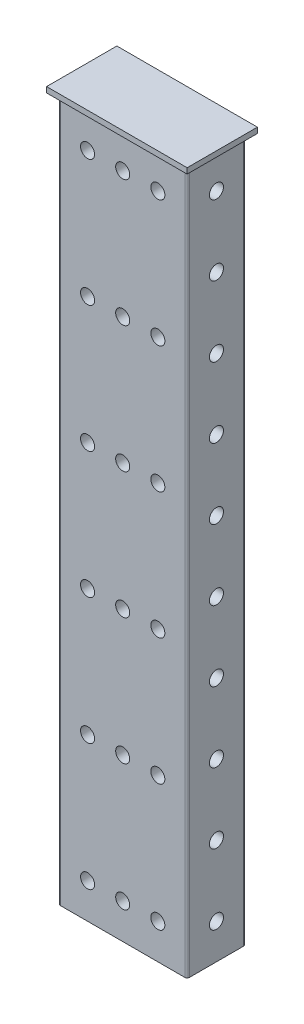
SolidWorks part; units mm, degrees
material "Nylon 101"
ref_plane "Front Plane" through (0, 0, 0) normal (0, 0, 1) x (1, 0, 0)
ref_plane "Top Plane" through (0, 0, 0) normal (0, 1, 0) x (1, 0, 0)
ref_plane "Right Plane" through (0, 0, 0) normal (1, 0, 0) x (0, 0, -1)
sketch "Sketch2" plane through (0, 0, 0) normal (0, 1, 0) x (1, 0, 0)
  line L1 (0, 0) -> (50.8, 0)
  line L2 (0, 0) -> (0, 25.4)
  line L3 (0, 25.4) -> (50.8, 25.4)
  line L12 (50.8, 0) -> (50.8, 25.4)
  line L14 (2.1082, 23.2918) -> (48.6918, 23.2918)
  line L15 (48.6918, 2.1082) -> (48.6918, 23.2918)
  line L16 (2.1082, 2.1082) -> (48.6918, 2.1082)
  line L17 (2.1082, 2.1082) -> (2.1082, 23.2918)
  dimension "D1" = 50.8
  dimension "D3" = 25.4
  dimension "D2" = 2.1082
extrude "Boss-Extrude2" add sketch "Sketch2" along normal blind 2 separate body contours L17 L16 L15 L14 | L16 L17 L14 L15 region at (0.568, 0, -12.7) region at (25.4, 0, -12.7)
extrude "Boss-Extrude3" add sketch "Sketch2<4>" against normal blind 254 contours L17 L16 L15 L14 region at (25.4, 0, -12.7)
sketch "Sketch2<4>" plane through (0, 0, 0) normal (0, 1, 0) x (1, 0, 0) same geometry as "Sketch2"
fillet "Fillet3" radius 0.8106 4 edges at (2.1082, -127, -23.2918) (48.6918, -127, -2.1082) (2.1082, -127, -2.1082) (48.6918, -127, -23.2918)
sketch "Sketch3" plane through (48.6918, 0, 0) normal (1, 0, 0) x (0, 0, -1)
  line L0 (2.9188, 0) -> (22.4812, 0) construction
  line L1 (2.9188, -254) -> (22.4812, -254) construction
  line L3 (12.7, 0) -> (12.7, -254) construction
  circle A0 centre (12.7, -12.7) radius 2.54
  point P4 (11.5292, -248.866)
  point P7 (12.7635, -2.6535)
  dimension "D3" = 5.08
  dimension "D1" = 12.7
extrude "Cut-Extrude1" cut sketch "Sketch3" against normal through all
sketch "Sketch4" plane through (0, 0, -23.2918) normal (0, 0, -1) x (-1, 0, 0)
  line L0 (-47.8812, -12.7) -> (-2.9188, -12.7) construction
  line L1 (-47.8812, 0) -> (-47.8812, -254) construction
  line L2 (-2.9188, -254) -> (-2.9188, 0) construction
  line L3 (-2.9188, 0) -> (-47.8812, 0) construction
  circle A0 centre (-25.4, -12.7) radius 2.54
  circle A1 centre (-38.1, -12.7) radius 2.54
  circle A2 centre (-12.7, -12.7) radius 2.54
  dimension "D2" = 5.08
  dimension "D1" = 12.7
  dimension "D3" = 12.7
  dimension "D4" = 12.7
extrude "Cut-Extrude2" cut sketch "Sketch4" against normal through all
pattern_linear "LPattern1" count 10 spacing 25.4 along (0, -1, 0) of "Cut-Extrude1"
pattern_linear "LPattern4" count 6 spacing 45.72 along (0, -1, 0) of "Cut-Extrude2"
equation "\"D2@Sketch2\"=0.063+0.02"
